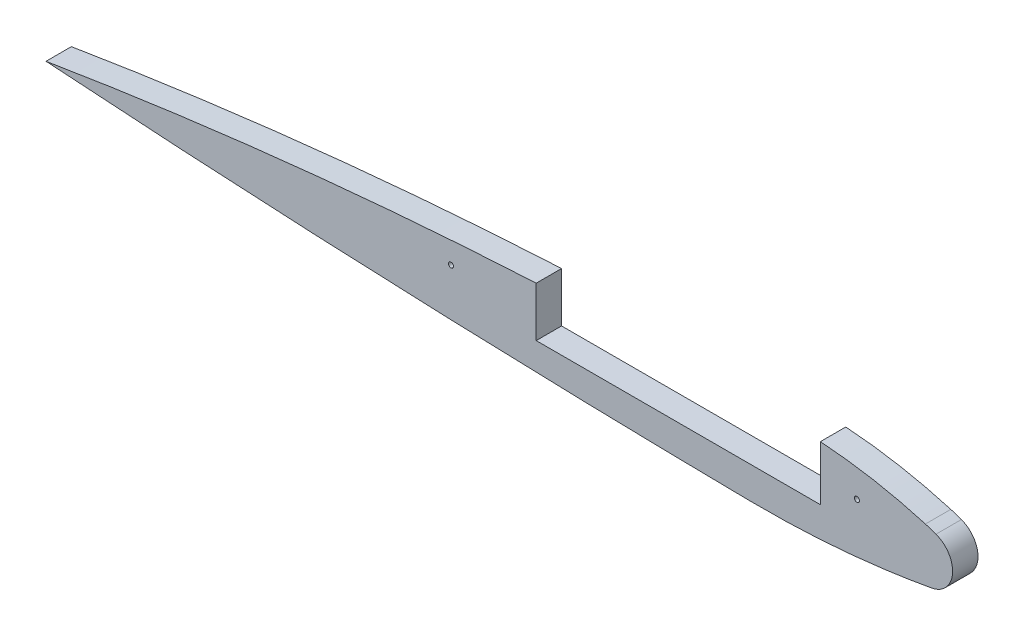
SolidWorks part; units mm, degrees
material "Carbon/Foam Panel"
ref_plane "Front Plane" through (0, 0, 0) normal (0, 0, 1) x (1, 0, 0)
ref_plane "Top Plane" through (0, 0, 0) normal (0, 1, 0) x (1, 0, 0)
ref_plane "Right Plane" through (0, 0, 0) normal (1, 0, 0) x (0, 0, -1)
sketch "Sketch1" plane through (0, 0, 0) normal (0, 0, 1) x (1, 0, 0)
  ellipse E1 centre (30.4917, -1212.2061) end of major axis (1372.9244, -1212.2061) minor radius 1244.6819 (36.9797, 32.4612) -> (-204.2943, 13.2914) ccw
  ellipse E3 centre (36.2563, -106.312) end of major axis (185.9298, -106.312) minor radius 138.7748 (81.5372, 25.9598) -> (36.9797, 32.4612) ccw
  ellipse E5 centre (65.7891, -20.0426) end of major axis (117.8436, -20.0426) minor radius 48.2641 (103.4339, 13.2914) -> (81.5372, 25.9598) ccw
  ellipse E7 centre (28.1769, 268.4704) end of major axis (313.5001, 268.4704) minor radius 264.5471 (24.2792, 3.948) -> (103.4339, 13.2914) ccw
  ellipse E9 centre (66.1797, 2847.5869) end of major axis (3464.1974, 2820.9695) minor radius 2843.9273 (-204.2943, 13.2914) -> (24.2792, 3.948) ccw
extrude "Boss-Extrude1" add sketch "Sketch1" along normal blind 6.35 contours E1 E9 E7 E5 E3
fillet "Fillet1" radius 6.35 1 edges at (103.4339, 13.2914, 3.175)
sketch "Sketch2" plane through (0, 0, 0) normal (0, 0, -1) x (-1, 0, 0)
  line L0 (46.0477, 25.527) -> (46.0477, 14.097) construction
  line L1 (10.4877, 25.527) -> (81.6077, 25.527)
  line L2 (10.4877, 25.527) -> (10.4877, 14.097)
  line L3 (10.4877, 14.097) -> (81.6077, 14.097)
  line L4 (81.6077, 25.527) -> (81.6077, 14.097)
  line L5 (81.6077, 19.812) -> (10.4877, 19.812) construction
  line L6 (13.0277, 25.527) -> (13.0277, 14.097) construction
  line L7 (3.4925, 0) -> (-3.4925, 0) construction
  dimension "D1" = 2.54
  dimension "D2" = 11.43
  dimension "D3" = 68.58
  dimension "D5" = 19.812
extrude "Cut-Extrude1" cut sketch "Sketch2" against normal through all
sketch "Sketch3" plane through (0, 0, 0) normal (0, 0, 1) x (1, 0, 0)
  line L0 (-10.4877, 25.527) -> (-10.4877, 14.097) construction
  line L2 (-102.9437, 19.812) -> (-1.3437, 19.812) construction
  circle A0 centre (-1.3437, 19.812) radius 0.635
  circle A1 centre (-102.9437, 19.812) radius 0.635
  point P7 (-10.4877, 19.812)
  dimension "D1" = 1.27
  dimension "D4" = 1.27
  dimension "D3" = 101.6
  dimension "D2" = 9.144
extrude "Cut-Extrude2" cut sketch "Sketch3" along normal through all
sketch "Sketch6" plane through (0, 0, 0) normal (0, 0, 1) x (1, 0, 0)
  ellipse E1 centre (-23.5091, -930.3417) end of major axis (1010.1641, -930.3417) minor radius 958.4051 (-18.5133, 28.0522) -> (-204.2943, 13.2914) ccw
  ellipse E3 centre (-19.0703, -78.8032) end of major axis (96.1783, -78.8032) minor radius 106.8566 (15.7959, 23.0461) -> (-18.5133, 28.0522) ccw
  ellipse E5 centre (3.6699, -12.3758) end of major axis (43.7519, -12.3758) minor radius 37.1633 (32.6564, 13.2914) -> (15.7959, 23.0461) ccw
  ellipse E7 centre (-25.2915, 209.7792) end of major axis (194.4074, 209.7792) minor radius 203.7012 (-28.2927, 6.097) -> (32.6564, 13.2914) ccw
  ellipse E9 centre (3.9707, 2195.6989) end of major axis (-2612.5029, 2216.1943) minor radius 2189.824 (-204.2943, 13.2914) -> (-28.2927, 6.097) ccw
extrude "Cut-Extrude4" cut sketch "Sketch6" along normal through all flip side to cut
fillet "Fillet3" radius 6.35 1 edges at (32.6564, 13.2914, 3.175)
sketch "Sketch8" plane through (0, 0, 0) normal (0, 0, 1) x (1, 0, 0)
  line L0 (-81.6077, 25.527) -> (-10.4877, 25.527) construction
  line L1 (-81.6077, 25.527) -> (-10.4877, 25.527)
  line L2 (-10.4877, 25.527) -> (-10.4877, 27.7567)
  line L3 (-81.6077, 25.527) -> (-81.6077, 26.5483)
  ellipse E0 centre (-23.5091, -930.3417) end of major axis (1010.1641, -930.3417) minor radius 958.4051 (-18.5133, 28.0522) -> (-204.2943, 13.2914) ccw construction
  ellipse E1 centre (-23.5091, -930.3417) end of major axis (1010.1641, -930.3417) minor radius 958.4051 (-18.5133, 28.0522) -> (-81.6077, 26.5483) ccw
  ellipse E2 centre (-19.0703, -78.8032) end of major axis (96.1783, -78.8032) minor radius 106.8566 (15.7959, 23.0461) -> (-18.5133, 28.0522) ccw construction
  ellipse E3 centre (-19.0703, -78.8032) end of major axis (96.1783, -78.8032) minor radius 106.8566 (-10.4877, 27.7567) -> (-18.5133, 28.0522) ccw
extrude "Cut-Extrude5" cut sketch "Sketch8" along normal through all
equation "\"D4@Sketch3\"=\"D1@Sketch3\""
